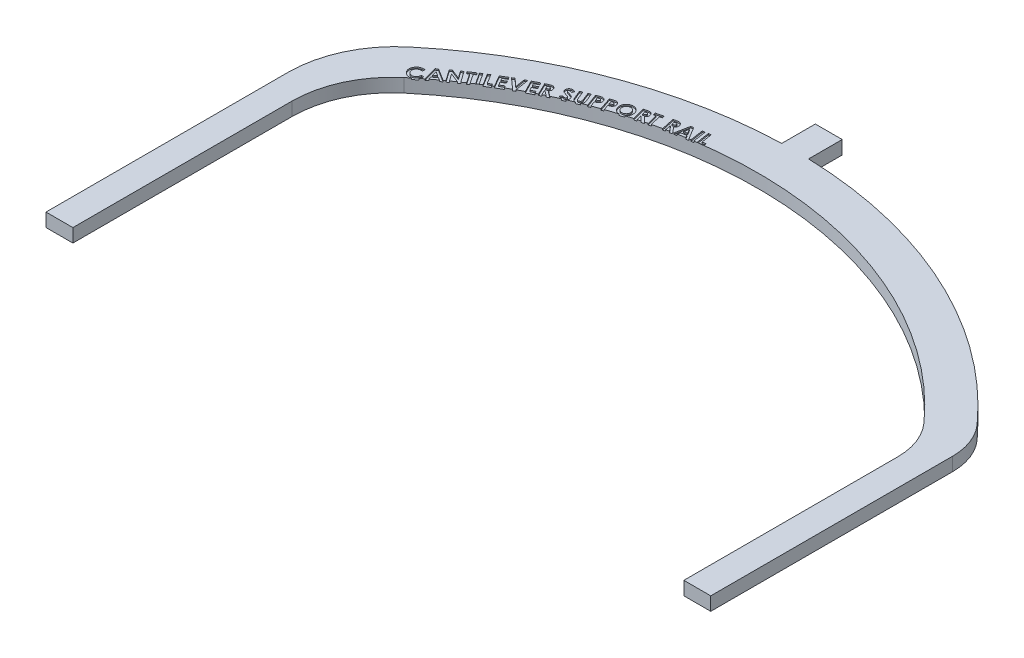
SolidWorks part; units mm, degrees
ref_plane "Front Plane" through (0, 0, 0) normal (0, 0, 1) x (1, 0, 0)
ref_plane "Top Plane" through (0, 0, 0) normal (0, 1, 0) x (1, 0, 0)
ref_plane "Right Plane" through (0, 0, 0) normal (1, 0, 0) x (0, 0, -1)
sketch "Sketch1" plane through (0, 0, 0) normal (0, 1, 0) x (1, 0, 0)
  line L2 (3095.3461, 587.5132) -> (3095.3461, 279.8321) construction
  line L3 (3082.6461, 1003.8795) -> (3082.6461, 1035.6295)
  line L4 (3082.6461, 1035.6295) -> (3108.0461, 1035.6295)
  line L5 (3108.0461, 1035.6295) -> (3108.0461, 1003.8795)
  line L6 (2827.5865, 906.6167) -> (2850.444, 879.3761) construction
  line L7 (2791.2937, 600.1865) -> (2816.6937, 600.1865)
  line L8 (2791.2937, 600.1865) -> (2791.2937, 828.7865)
  line L10 (2816.6937, 600.1865) -> (2816.6937, 806.9983)
  line L12 (3393.89, 802.3188) -> (3393.89, 600.1865)
  line L13 (3393.89, 600.1865) -> (3419.29, 600.1865)
  line L14 (3419.29, 828.7865) -> (3419.29, 600.1865)
  line L15 (3404.9105, 866.2462) -> (3378.4843, 842.4519) construction
  arc A0 (2827.5865, 906.6167) -> (3082.6461, 1003.8795) centre (3095.3461, 587.5132) cw
  arc A1 (2850.444, 879.3761) -> (3378.4843, 842.4519) centre (3095.3461, 587.5132) cw
  arc A2 (3108.0461, 1003.8795) -> (3404.9105, 866.2462) centre (3095.3461, 587.5132) cw
  arc A3 (2827.5865, 906.6167) -> (2791.2937, 828.7865) centre (2892.8937, 828.7865) ccw
  arc A4 (2850.444, 879.3761) -> (2816.6937, 806.9983) centre (2911.1762, 806.9983) ccw
  arc A5 (3378.4843, 842.4519) -> (3393.89, 802.3188) centre (3333.912, 802.3188) cw
  arc A6 (3404.9105, 866.2462) -> (3419.29, 828.7865) centre (3363.3073, 828.7865) cw
  circle A7 centre (3044.5461, 584.9732) radius 60.7995 construction
  dimension "D1" = 381
  dimension "D4" = 101.6
  dimension "D2" = 35.56
  dimension "D3" = 228.6
  dimension "D5" = 25.4
  dimension "D6" = 31.75
  dimension "D7" = 40
  dimension "D8" = 48
  dimension "D9" = 50.8
  dimension "D10" = 2.54
  dimension "D11" = 25.4
  dimension "D12" = 25.4
extrude "Boss-Extrude1" add sketch "Sketch1" along normal blind 12.7
sketch "Sketch2" plane through (0, 12.7, 0) normal (0, 1, 0) x (1, 0, 0)
  text T0 "CANTILEVER SUPPORT RAIL" font "Century Gothic" height 12.7
extrude "Cut-Extrude1" cut sketch "Sketch2" against normal blind 1.27
